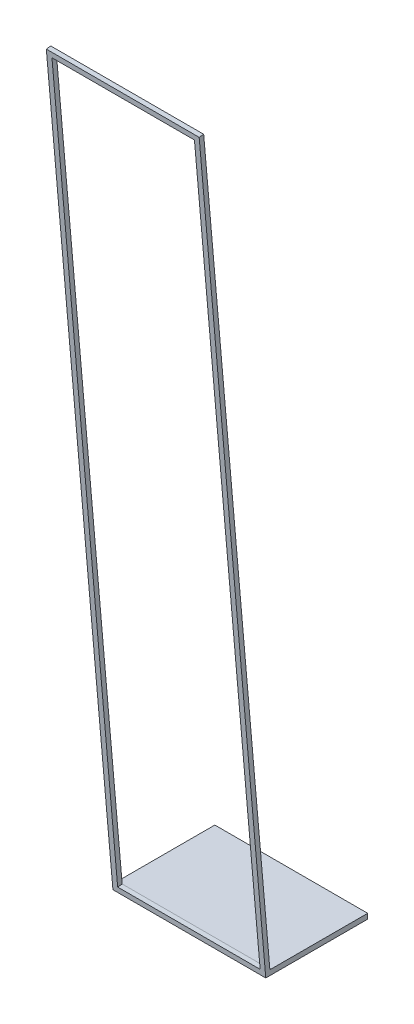
SolidWorks part; units mm, degrees
ref_plane "Front Plane" through (0, 0, 0) normal (0, 0, 1) x (1, 0, 0)
ref_plane "Top Plane" through (0, 0, 0) normal (0, 1, 0) x (1, 0, 0)
ref_plane "Right Plane" through (0, 0, 0) normal (1, 0, 0) x (0, 0, -1)
sketch "Sketch2" plane through (0, 0, 0) normal (0, 1, 0) x (1, 0, 0)
  line L1 (-1500, 2000) -> (1500, 2000)
  line L2 (-1500, 2000) -> (-1500, 0)
  line L3 (-1500, 0) -> (1500, 0)
  line L4 (1500, 2000) -> (1500, 0)
  dimension "D1" = 2000
  dimension "D2" = 3000
extrude "Boss-Extrude1" add sketch "Sketch2" along normal blind 100
sketch "Sketch3" plane through (0, 0, 0) normal (1, 0, 0) x (0, 0, -1)
  line L0 (0, 0) -> (-1307.3361, 14942.9205)
  line L1 (-1307.3361, 14942.9205) -> (-1218.7744, 14950.6686)
  line L2 (-1218.7744, 14950.6686) -> (89.2396, 0)
  line L3 (0, 0) -> (2000, 0) construction
  line L4 (89.2396, 0) -> (0, 0)
  line L5 (0, 100) -> (0, 0) construction
  dimension "D1" = 5
  dimension "D2" = 88.9
  dimension "D3" = 15000
extrude "Boss-Extrude2" add sketch "Sketch3" along normal through all and the other way through all
sketch "Sketch4" plane through (0, 0, 0) normal (0, -0.0872, 0.9962) x (1, 0, 0)
  line L0 (-1500, 0) -> (1500, 15000) construction
  line L1 (-1398.4, 14898.4) -> (1398.4, 14898.4)
  line L2 (-1398.4, 14898.4) -> (-1398.4, 101.6)
  line L3 (-1398.4, 101.6) -> (1398.4, 101.6)
  line L4 (1398.4, 14898.4) -> (1398.4, 101.6)
  line L5 (1398.4, 101.6) -> (-1398.4, 14898.4) construction
  line L6 (1500, 15000) -> (-1500, 15000) construction
  line L7 (-1500, 15000) -> (-1500, 0) construction
  point P8 (0, 7500)
  dimension "D1" = 101.6
  dimension "D2" = 101.6
extrude "Cut-Extrude1" cut sketch "Sketch4" against normal through all
